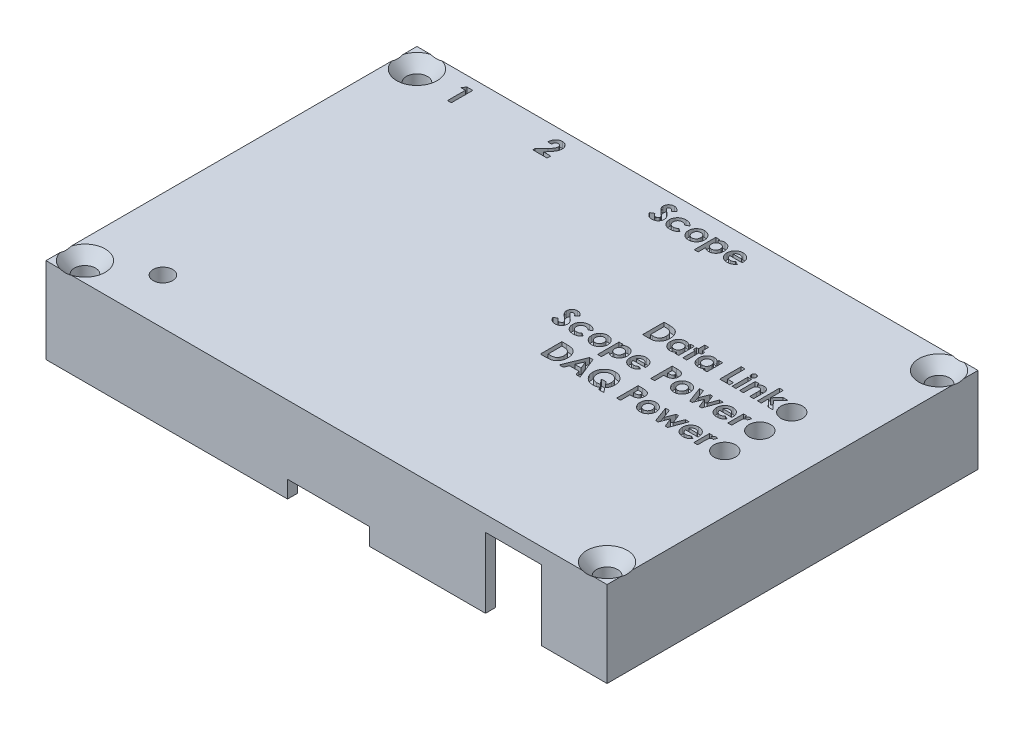
SolidWorks part; units mm, degrees
ref_plane "Front Plane" through (0, 0, 0) normal (0, 0, 1) x (1, 0, 0)
ref_plane "Top Plane" through (0, 0, 0) normal (0, 1, 0) x (1, 0, 0)
ref_plane "Right Plane" through (0, 0, 0) normal (1, 0, 0) x (0, 0, -1)
sketch "Sketch1" plane through (0, 0, 0) normal (0, 1, 0) x (1, 0, 0)
  line L1 (45.72, 30.226) -> (-45.72, 30.226)
  line L2 (45.72, 30.226) -> (45.72, -30.226)
  line L3 (45.72, -30.226) -> (-45.72, -30.226)
  line L4 (-45.72, 30.226) -> (-45.72, -30.226)
  line L5 (45.72, 30.226) -> (-45.72, -30.226) construction
  line L6 (45.72, -30.226) -> (-45.72, 30.226) construction
  point P0 (0, 0)
  dimension "D1" = 60.452
  dimension "D2" = 91.44
extrude "Boss-Extrude1" add sketch "Sketch1" along normal blind 13.97
sketch "Sketch2" plane through (0, 0, 0) normal (0, -1, 0) x (1, 0, 0)
  line L0 (45.72, -30.226) -> (-45.72, -30.226) construction
  line L1 (39.37, 28.575) -> (-39.37, 28.575)
  line L2 (39.37, 28.575) -> (39.37, -28.575)
  line L3 (39.37, -28.575) -> (-39.37, -28.575)
  line L4 (-39.37, 28.575) -> (-39.37, -28.575)
  line L5 (39.37, 28.575) -> (-39.37, -28.575) construction
  line L6 (39.37, -28.575) -> (-39.37, 28.575) construction
  line L7 (-45.72, -30.226) -> (-45.72, 30.226) construction
  point P0 (0, 0)
  dimension "D1" = 1.651
  dimension "D2" = 57.15
  dimension "D3" = 78.74
  dimension "D4" = 6.35
extrude "Cut-Extrude1" cut sketch "Sketch2" against normal offset from surface (11.43 mm away) 2.54 up to face at (0, 13.97, 0)
sketch "Sketch3" plane through (0, 0, 0) normal (0, -1, 0) x (1, 0, 0)
  line L0 (42.545, 27.051) -> (-42.545, 27.051) construction
  line L1 (42.545, 27.051) -> (42.545, -27.051) construction
  line L2 (42.545, -27.051) -> (-42.545, -27.051) construction
  line L3 (-42.545, 27.051) -> (-42.545, -27.051) construction
  line L4 (42.545, 27.051) -> (-42.545, -27.051) construction
  line L5 (42.545, -27.051) -> (-42.545, 27.051) construction
  line L6 (-45.72, 30.226) -> (45.72, 30.226) construction
  line L7 (-45.72, -30.226) -> (-45.72, 30.226) construction
  line L9 (-45.72, -30.226) -> (-45.72, 30.226) construction
  line L10 (39.37, 28.575) -> (-39.37, 28.575) construction
  circle A0 centre (-42.545, 27.051) radius 1.7145
  circle A1 centre (-42.545, -27.051) radius 1.7145
  circle A2 centre (42.545, -27.051) radius 1.7145
  circle A3 centre (42.545, 27.051) radius 1.7145
  circle A4 centre (-34.163, 22.733) radius 1.5875
  point P0 (0, 0)
  dimension "D1" = 3.429
  dimension "D5" = 11.557
  dimension "D6" = 3.175
  dimension "D2" = 3.175
  dimension "D3" = 3.175
  dimension "D4" = 5.842
extrude "Cut-Extrude2" cut sketch "Sketch3" against normal through all
chamfer "Chamfer1" distance 1.905 distance2 1.5875 4 edges at (42.545, 13.97, -28.7655) (42.545, 13.97, 25.3365) (-42.545, 13.97, 25.3365) (-42.545, 13.97, -28.7655) first distance on face at (42.545, 13.97, -28.7655) first distance on face at (42.545, 13.97, 25.3365) first distance on face at (-42.545, 13.97, 25.3365) first distance on face at (-42.545, 13.97, -28.7655)
sketch "Sketch4" plane through (0, 0, 30.226) normal (0, 0, 1) x (1, 0, 0)
  line L0 (-45.72, 0) -> (45.72, 0) construction
  line L1 (-6.35, 0) -> (6.985, 0)
  line L2 (-6.35, 0) -> (-6.35, 2.794)
  line L3 (-6.35, 2.794) -> (6.985, 2.794)
  line L4 (6.985, 0) -> (6.985, 2.794)
  line L5 (45.72, 13.97) -> (45.72, 0) construction
  line L6 (-45.72, 13.97) -> (-45.72, 0) construction
  line L7 (35.052, 11.43) -> (25.908, 11.43)
  line L8 (35.052, 11.43) -> (35.052, 0)
  line L9 (35.052, 0) -> (25.908, 0)
  line L10 (25.908, 11.43) -> (25.908, 0)
  line L11 (35.052, 11.43) -> (25.908, 0) construction
  line L12 (35.052, 0) -> (25.908, 11.43) construction
  point P8 (30.48, 5.715)
  dimension "D1" = 13.335
  dimension "D2" = 2.794
  dimension "D3" = 52.07
  dimension "D4" = 76.2
  dimension "D5" = 11.43
  dimension "D6" = 9.144
extrude "Cut-Extrude3" cut sketch "Sketch4" against normal up to next
sketch "Sketch5" plane through (0, 0, -30.226) normal (0, 0, -1) x (-1, 0, 0)
  line L0 (-45.72, 0) -> (45.72, 0) construction
  line L5 (-3.048, 6.604) -> (20.32, 6.604) construction
  line L6 (20.32, 6.604) -> (35.179, 6.604) construction
  line L7 (45.72, 13.97) -> (45.72, 0) construction
  line L9 (-6.223, 6.604) -> (-6.223, 0)
  line L10 (-6.223, 0) -> (0.127, 0)
  line L11 (0.127, 6.604) -> (0.127, 0)
  line L12 (-27.0547, 10.0965) -> (-31.3653, 10.0965)
  line L13 (17.145, 6.604) -> (17.145, 0)
  line L14 (17.145, 0) -> (23.495, 0)
  line L15 (23.495, 6.604) -> (23.495, 0)
  line L16 (-45.72, 13.97) -> (-45.72, 0) construction
  line L17 (32.004, 6.604) -> (32.004, 0)
  line L18 (32.004, 0) -> (38.354, 0)
  line L19 (38.354, 6.604) -> (38.354, 0)
  line L20 (-41.638, 13.97) -> (41.638, 13.97) construction
  arc A0 (0.127, 6.604) -> (-6.223, 6.604) centre (-3.048, 6.604) ccw
  arc A1 (23.495, 6.604) -> (17.145, 6.604) centre (20.32, 6.604) ccw
  arc A2 (38.354, 6.604) -> (32.004, 6.604) centre (35.179, 6.604) ccw
  arc A3 (-31.3653, 10.0965) -> (-27.0547, 10.0965) centre (-29.21, 7.4295) ccw
  dimension "D1" = 6.35
  dimension "D9" = 6.858
  dimension "D4" = 6.604
  dimension "D5" = 10.541
  dimension "D6" = 25.4
  dimension "D8" = 48.768
  dimension "D10" = 2.667
  dimension "D11" = 16.51
  dimension "D12" = 6.5405
extrude "Cut-Extrude4" cut sketch "Sketch5" against normal up to next
fillet "Fillet1" radius 1.5875 4 edges at (-39.37, 5.715, -28.575) (-39.37, 5.715, 28.575) (39.37, 5.715, 28.575) (39.37, 5.715, -28.575)
sketch "Sketch6" plane through (0, 11.43, 0) normal (0, -1, 0) x (1, 0, 0)
  line L1 (36.449, -9.144) -> (36.449, -3.937) construction
  line L2 (36.449, -3.937) -> (36.449, 1.778) construction
  line L3 (-45.72, -26.144) -> (-45.72, 26.144) construction
  line L4 (37.7825, 28.575) -> (35.052, 28.575) construction
  circle A0 centre (36.449, -9.144) radius 1.75
  circle A1 centre (36.449, -3.937) radius 1.75
  circle A2 centre (36.449, 1.778) radius 1.75
  dimension "D1" = 3.5
  dimension "D2" = 82.169
  dimension "D3" = 26.797
  dimension "D4" = 5.715
  dimension "D5" = 5.207
extrude "Cut-Extrude5" cut sketch "Sketch6" against normal up to next
sketch "Sketch7" plane through (0, 13.97, 0) normal (0, 1, 0) x (1, 0, 0)
  line L0 (-36.7154, 25.0796) -> (-21.7777, 25.0796) construction
  line L1 (-21.7777, 25.0796) -> (-3.4493, 25.0796) construction
  line L2 (12.9339, 7.9504) -> (3.4502, 7.9504) construction
  line L3 (3.4502, 7.9504) -> (3.4502, 2.4137) construction
  line L4 (3.4502, 2.4137) -> (3.4502, -3.123) construction
  line L5 (3.4502, -3.123) -> (7.3459, -3.123) construction
  text T0 "<b>Data Link</b>"
  text T1 "<b>Scope Power</b>"
  text T2 "<b>DAQ Power</b>"
  text T3 "<b>1</b>"
  text T4 "<b>2</b>"
  text T5 "<b>Scope</b>"
extrude "Cut-Extrude6" cut sketch "Sketch7" against normal blind 1
sketch "Sketch8" plane through (-45.72, 0, 0) normal (-1, 0, 0) x (0, 0, 1)
  text T0 "<b>Miniscope DAQ Box v3.2</b>"
extrude "Cut-Extrude7" cut sketch "Sketch8" against normal blind 1
